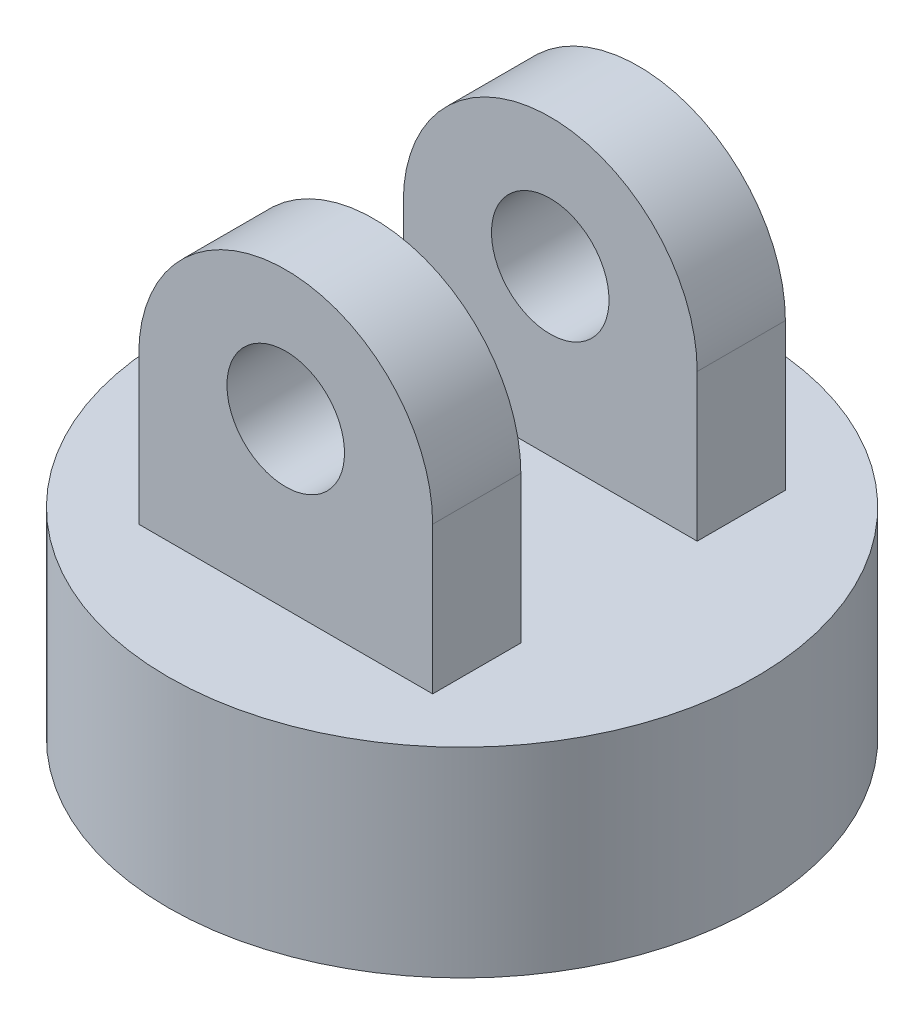
SolidWorks part; units mm, degrees
ref_plane "Alzado" through (0, 0, 0) normal (0, 0, 1) x (1, 0, 0)
ref_plane "Planta" through (0, 0, 0) normal (0, 1, 0) x (1, 0, 0)
ref_plane "Vista lateral" through (0, 0, 0) normal (1, 0, 0) x (0, 0, -1)
sketch "Croquis1" plane through (0, 0, 0) normal (0, 1, 0) x (1, 0, 0)
  circle A0 centre (0, 0) radius 50
  dimension "D1" = 100
extrude "Saliente-Extruir1" add sketch "Croquis1" along normal blind 34
sketch "Croquis2" plane through (0, 34, 0) normal (0, 1, 0) x (1, 0, 0)
  line L0 (-50, 0) -> (50, 0) construction
  line L1 (0, 50) -> (0, -50) construction
  line L2 (-25, 30) -> (25, 30)
  line L3 (25, 30) -> (25, 15)
  line L4 (25, 15) -> (-25, 15)
  line L5 (-25, 15) -> (-25, 30)
  line L6 (-25, -15) -> (-25, -30)
  line L7 (-25, -30) -> (25, -30)
  line L8 (25, -30) -> (25, -15)
  line L9 (25, -15) -> (-25, -15)
  circle A0 centre (0, 0) radius 50 construction
  point P13 (25, 22.5)
  dimension "D1" = 30
  dimension "D2" = 15
  dimension "D3" = 50
  dimension "D4" = 50
  dimension "D5" = 25
  dimension "D6" = 60
  dimension "D7" = 15
extrude "Saliente-Extruir2" add sketch "Croquis2" along normal blind 50
sketch "Croquis4" plane through (0, 0, -30) normal (0, 0, -1) x (-1, 0, 0)
  line L0 (25, 84) -> (25, 34) construction
  line L1 (-25, 84) -> (25, 84) construction
  circle A0 centre (0, 62) radius 10
  dimension "D1" = 20
  dimension "D2" = 25
  dimension "D3" = 22
extrude "Cortar-Extruir1" cut sketch "Croquis4" against normal blind 60
fillet "Redondeo1" 2 edges at (25, 84, -22.5) (-25, 84, -22.5) type full round first side face at (25, 59, -22.5) second side face at (-25, 59, -22.5) middle face at (0, 84, -22.5)
fillet "Redondeo2" 2 edges at (25, 84, 22.5) (-25, 84, 22.5) type full round first side face at (25, 59, 22.5) second side face at (-25, 59, 22.5) middle face at (0, 84, 22.5)
